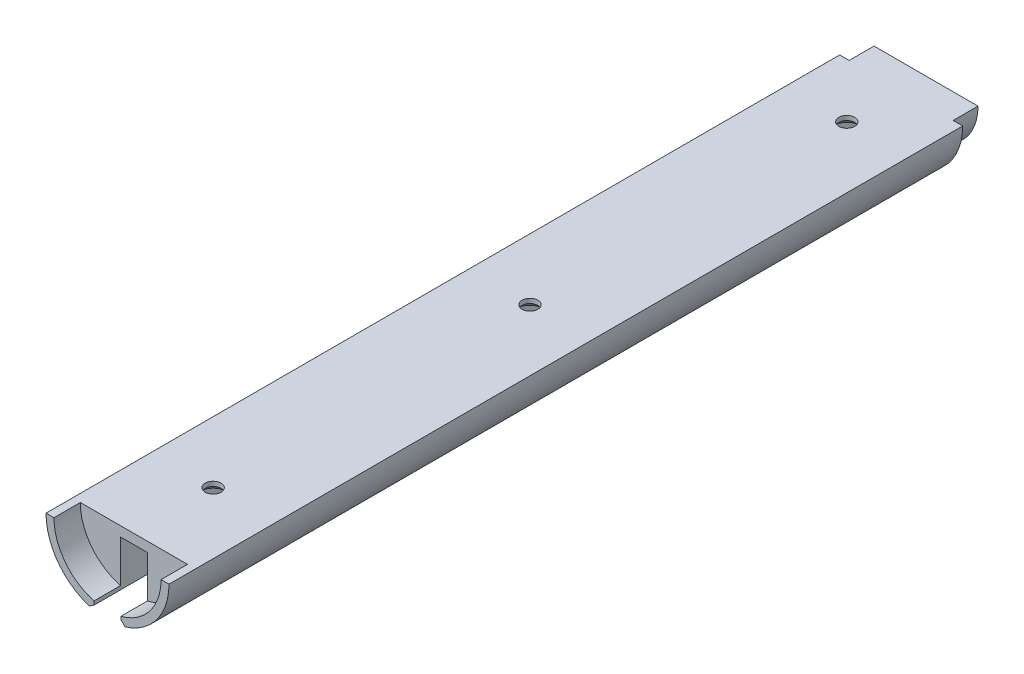
SolidWorks part; units mm, degrees
ref_plane "Front Plane" through (0, 0, 0) normal (0, 0, 1) x (1, 0, 0)
ref_plane "Top Plane" through (0, 0, 0) normal (0, 1, 0) x (1, 0, 0)
ref_plane "Right Plane" through (0, 0, 0) normal (1, 0, 0) x (0, 0, -1)
sketch "Sketch1" plane through (0, 0, 0) normal (0, 0, 1) x (1, 0, 0)
  line L1 (-14.7902, 8.509) -> (14.7902, 8.509)
  line L2 (3.0226, 5.969) -> (-3.0226, 5.969) construction
  line L11 (3.2131, -6.1595) -> (3.2131, 6.1595)
  line L12 (3.2131, 6.1595) -> (-3.2131, 6.1595)
  line L13 (-3.2131, 6.1595) -> (-3.2131, -6.1595)
  line L14 (-3.2131, -6.1595) -> (3.2131, -6.1595)
  line L15 (3.2131, -6.1595) -> (3.2131, 6.1595)
  line L16 (3.2131, 6.1595) -> (-3.2131, 6.1595)
  line L17 (-3.2131, 6.1595) -> (-3.2131, -6.1595)
  line L18 (-3.2131, -6.1595) -> (3.2131, -6.1595)
  arc A0 (-14.7902, 8.509) -> (14.7902, 8.509) centre (0, 8.509) ccw
  dimension "D1" = 2.54
  dimension "D2" = 0.1905
extrude "Boss-Extrude1" add sketch "Sketch1" along normal mid plane 196.85 contours L1 A0 L17 L16 L15 region at (0, 8.1798, 0)
sketch "Sketch2" plane through (0, 0, 98.425) normal (0, 0, 1) x (1, 0, 0)
  line L0 (-14.7902, 8.509) -> (14.7902, 8.509) construction
  line L1 (-12.8852, 8.509) -> (12.8852, 8.509)
  circle A0 centre (0, 8.509) radius 12.8852
  arc A2 (-14.7902, 8.509) -> (-3.2131, -5.9279) centre (0, 8.509) ccw construction
  line M2 (14.7902, 8.509) -> (-14.7902, 8.509)
  line M4 (-3.2131, -5.9279) -> (-3.2131, 6.1595)
  line M5 (-3.2131, 6.1595) -> (3.2131, 6.1595)
  line M6 (3.2131, 6.1595) -> (3.2131, -5.9279)
  dimension "D1" = 1.905
extrude "Cut-Extrude1" cut sketch "Sketch2" against normal blind 6.35 contours A0 M2 M4 M5 M6 region at (0, 8.2227, 98.425)
sketch "Sketch3" plane through (0, 0, -98.425) normal (0, 0, -1) x (-1, 0, 0)
  line L8 (12.8852, 8.509) -> (-12.8852, 8.509)
  line L9 (3.2131, 6.1595) -> (3.2131, -3.9691)
  line L10 (-3.2131, 6.1595) -> (3.2131, 6.1595)
  line L11 (-3.2131, -3.9691) -> (-3.2131, 6.1595)
  line L12 (12.8852, 8.509) -> (-12.8852, 8.509)
  line L13 (3.2131, 6.1595) -> (3.2131, -3.9691)
  line L14 (-3.2131, 6.1595) -> (3.2131, 6.1595)
  line L15 (-3.2131, -3.9691) -> (-3.2131, 6.1595)
  line L16 (14.7902, 8.509) -> (-14.7902, 8.509)
  line L17 (-3.2131, -5.9279) -> (-3.2131, 6.1595)
  line L18 (-3.2131, 6.1595) -> (3.2131, 6.1595)
  line L19 (3.2131, 6.1595) -> (3.2131, -5.9279)
  line L20 (14.7902, 8.509) -> (-14.7902, 8.509)
  line L21 (-3.2131, -5.9279) -> (-3.2131, 6.1595)
  line L22 (-3.2131, 6.1595) -> (3.2131, 6.1595)
  line L23 (3.2131, 6.1595) -> (3.2131, -5.9279)
  circle A2 centre (0, 8.509) radius 12.5042
  arc A4 (3.2131, -3.9691) -> (12.8852, 8.509) centre (0, 8.509) ccw
  arc A5 (-12.8852, 8.509) -> (-3.2131, -3.9691) centre (0, 8.509) ccw
  arc A6 (3.2131, -3.9691) -> (12.8852, 8.509) centre (0, 8.509) ccw
  arc A7 (-12.8852, 8.509) -> (-3.2131, -3.9691) centre (0, 8.509) ccw
  arc A9 (-14.7902, 8.509) -> (-3.2131, -5.9279) centre (0, 8.509) ccw
  arc A10 (3.2131, -5.9279) -> (14.7902, 8.509) centre (0, 8.509) ccw
  arc A11 (-14.7902, 8.509) -> (-3.2131, -5.9279) centre (0, 8.509) ccw
  arc A12 (3.2131, -5.9279) -> (14.7902, 8.509) centre (0, 8.509) ccw
  line M14 (14.7902, 8.509) -> (-14.7902, 8.509)
  arc M15 (-14.7902, 8.509) -> (-3.2131, -5.9279) centre (0, 8.509) ccw
  line M16 (-3.2131, -5.9279) -> (-3.2131, 6.1595)
  line M18 (3.2131, 6.1595) -> (3.2131, -5.9279)
  arc M19 (3.2131, -5.9279) -> (14.7902, 8.509) centre (0, 8.509) ccw
  dimension "D2" = 0.381
  dimension "D1" = 0
  dimension "D3" = 0
extrude "Cut-Extrude2" cut sketch "Sketch3" against normal blind 5.969 contours A6 M18 M19 M14 | A7 M14 M15 M16 | A7 A2 M14 M16 | L23 A6 A2 M14 region at (-10.0592, 0.7119, -98.425) region at (-13.8377, 8.3239, -98.425) region at (10.0381, 0.7912, -98.425) region at (10.3303, 0.5018, -98.425)
sketch "Sketch4" plane through (0, 6.1595, 0) normal (0, -1, 0) x (1, 0, 0)
  line L1 (0, -98.425) -> (0, 92.075) construction
  line L2 (3.2131, -98.425) -> (-3.2131, -98.425) construction
  line L3 (-3.2131, 92.075) -> (3.2131, 92.075) construction
  line L4 (0, -3.175) -> (-3.2131, -3.175) construction
  line L5 (-3.2131, 92.075) -> (-3.2131, -98.425) construction
  circle A0 centre (0, -79.375) radius 1.905
  circle A1 centre (0, 73.025) radius 1.905
  circle A2 centre (0, -3.175) radius 1.905
  dimension "D1" = 3.81
  dimension "D2" = 76.2
extrude "Cut-Extrude3" cut sketch "Sketch4" against normal through all
chamfer "Chamfer1" distance 1.27 angle 45 2 edges at (3.2131, -5.9279, 2.9845) (-3.2131, -5.9279, 2.9845) first distance on face at (3.2131, -1.8282, -0.0952) first distance on face at (-10.27, 0.2734, 2.9845)
chamfer "Chamfer2" distance 1.27 angle 45 3 edges at (0, 6.1595, 74.93) (0, 6.1595, -81.28) (0, 6.1595, -5.08)
sketch "Sketch5" plane through (-3.2131, 0, 0) normal (1, 0, 0) x (0, 0, -1)
  line L0 (53.2413, 3.6195) -> (-53.2413, 3.6195) construction
  line L1 (-92.075, 6.1595) -> (98.425, 6.1595) construction
  text T0 "<b>Ceiling LED Mount V2</b>\r\n" font "Century Gothic" height 3.81
  point P2 (0, 3.6195)
  dimension "D1" = 2.54
extrude "Cut-Extrude4" cut sketch "Sketch5" against normal blind 0.635
